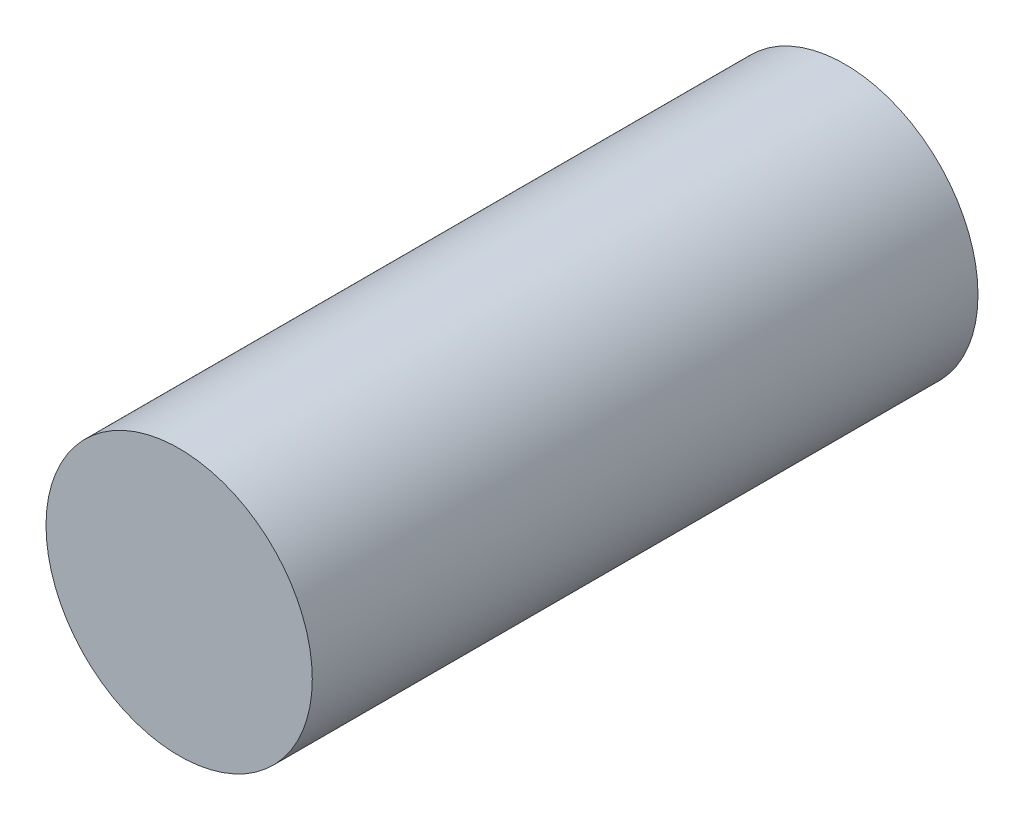
SolidWorks part; units mm, degrees
ref_plane "Front Plane" through (0, 0, 0) normal (0, 0, 1) x (1, 0, 0)
ref_plane "Top Plane" through (0, 0, 0) normal (0, 1, 0) x (1, 0, 0)
ref_plane "Right Plane" through (0, 0, 0) normal (1, 0, 0) x (0, 0, -1)
sketch "Sketch1" plane through (0, 0, 0) normal (0, 0, 1) x (1, 0, 0)
  circle A0 centre (0, 0) radius 5
  dimension "D1" = 10
extrude "Boss-Extrude1" add sketch "Sketch1" along normal blind 25
